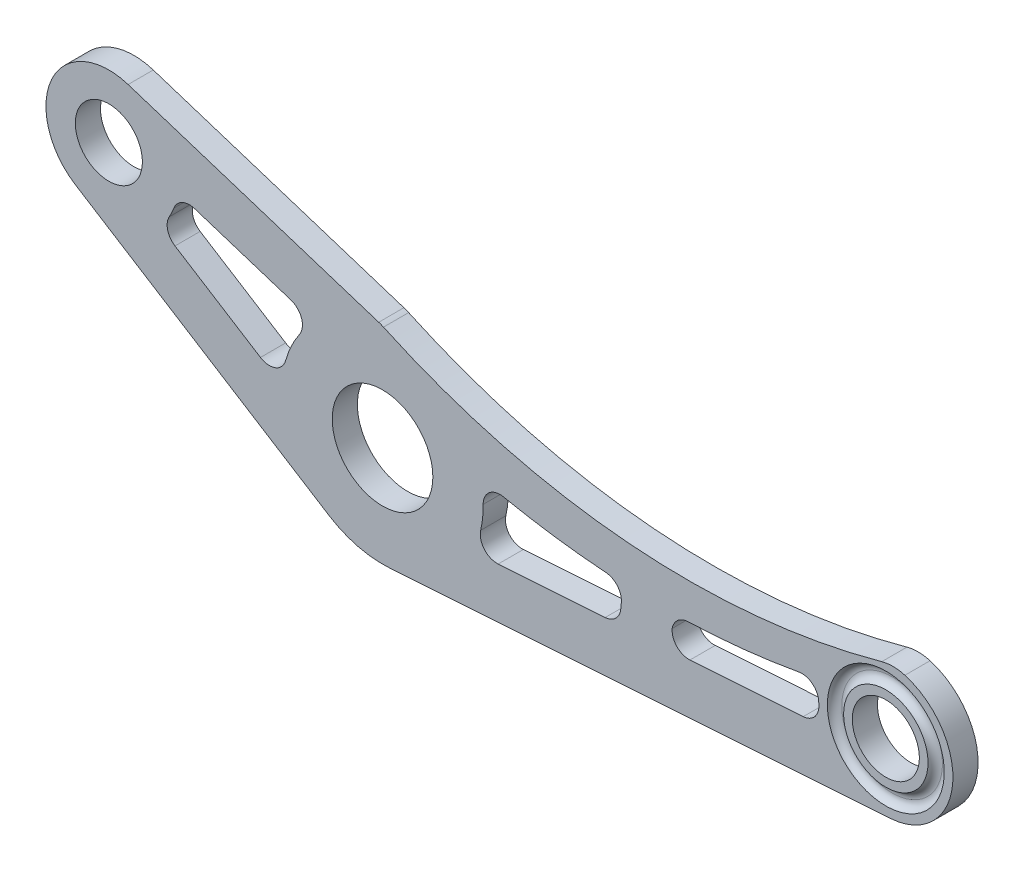
SolidWorks part; units mm, degrees
material "6061 合金"
ref_plane "前视基准面" through (0, 0, 0) normal (0, 0, 1) x (1, 0, 0)
ref_plane "上视基准面" through (0, 0, 0) normal (0, 1, 0) x (1, 0, 0)
ref_plane "右视基准面" through (0, 0, 0) normal (1, 0, 0) x (0, 0, -1)
other "Configuration Table"
sketch "草图1" plane through (0, 0, 0) normal (0, 0, 1) x (1, 0, 0)
  line L0 (0, 0) -> (60, 0)
  line L1 (0, 0) -> (-32.6271, 15.2143)
  line L2 (60.5333, -7.9822) -> (0.8, -11.9733)
  line L3 (4.7194, 11.7114) -> (60.5333, 7.9822)
  line L4 (-36.6215, 8.8665) -> (-6.3911, -10.1565)
  line L5 (-30.332, 22.3545) -> (-0.0675, 12.6264)
  arc A0 (-6.3911, -10.1565) -> (0.8, -11.9733) centre (0, 0) ccw
  arc A1 (-30.332, 22.3545) -> (-36.6215, 8.8665) centre (-32.6271, 15.2143) ccw
  arc A2 (60.5333, -7.9822) -> (60.5333, 7.9822) centre (60, 0) ccw
  arc A4 (4.7194, 11.7114) -> (-0.0675, 12.6264) centre (6.0528, 31.6669) cw
  dimension "D4" = 16
  dimension "D5" = 15
  dimension "D6" = 24
  dimension "D7" = 20
  dimension "D1" = 60
  dimension "D2" = 36
  dimension "D3" = 155
extrude "凸台-拉伸1" add sketch "草图1" along normal blind 3 contours L3 A4 L5 A1 L4 A0 L2 A2 region at (12.4558, 2.833, 0)
sketch "草图2" plane through (0, 0, 3) normal (0, 0, 1) x (1, 0, 0)
  circle A0 centre (-32.6271, 15.2143) radius 4
  circle A1 centre (60, 0) radius 4
  circle A2 centre (0, 0) radius 6
  dimension "D1" = 8
  dimension "D2" = 8
  dimension "D3" = 12
extrude "切除-拉伸1" cut sketch "草图2" against normal blind 5
sketch "草图3" plane through (0, 0, 3) normal (0, 0, 1) x (1, 0, 0)
  line L4 (32.6264, 9.8468) -> (30.6667, -9.9778)
  line L5 (4.7194, 11.7114) -> (60.5333, 7.9822) construction
  line L6 (60.5333, -7.9822) -> (0.8, -11.9733) construction
  line L7 (29.6409, 10.1419) -> (27.6812, -9.6826)
  line L8 (60.1333, 1.9956) -> (4.3194, 5.7248)
  line L9 (-1.9036, 6.9142) -> (-32.1681, 16.6423)
  line L10 (-33.426, 13.9447) -> (-3.1956, -5.0782)
  line L11 (0.4, -5.9867) -> (60.1333, -1.9956)
  line L12 (60.1333, 1.9956) -> (4.3194, 5.7248)
  line L13 (-1.9036, 6.9142) -> (-32.1681, 16.6423)
  line L14 (-33.426, 13.9447) -> (-3.1956, -5.0782)
  line L15 (0.4, -5.9867) -> (60.1333, -1.9956)
  line L16 (35.6118, 9.5517) -> (33.6521, -10.2729)
  circle A4 centre (0, 0) radius 12
  circle A5 centre (-32.6271, 15.2143) radius 8.2703
  circle A6 centre (60, 0) radius 8
  arc A8 (-1.9036, 6.9142) -> (4.3194, 5.7248) centre (6.0528, 31.6669) ccw
  arc A9 (-32.1681, 16.6423) -> (-33.426, 13.9447) centre (-32.6271, 15.2143) ccw
  arc A10 (-3.1956, -5.0782) -> (0.4, -5.9867) centre (0, 0) ccw
  arc A11 (60.1333, -1.9956) -> (60.1333, 1.9956) centre (60, 0) ccw
  arc A12 (-1.9036, 6.9142) -> (4.3194, 5.7248) centre (6.0528, 31.6669) ccw
  arc A13 (-32.1681, 16.6423) -> (-33.426, 13.9447) centre (-32.6271, 15.2143) ccw
  arc A14 (-3.1956, -5.0782) -> (0.4, -5.9867) centre (0, 0) ccw
  arc A15 (60.1333, -1.9956) -> (60.1333, 1.9956) centre (60, 0) ccw
  dimension "D1" = 6
  dimension "D2" = 3
  dimension "D3" = 3
extrude "切除-拉伸2" cut sketch "草图3" against normal blind 10 contours A4 L15 L7 L12 | A5 L14 A4 L13 | A6 L12 L16 L15 region at (42.8536, -0.0306, 3) region at (19.771, 0.0286, 3) region at (-17.2239, 8.0316, 3)
fillet "圆角1" radius 2 12 edges at (52.4046, -2.5119, 1.5) (34.2997, -3.7216, 1.5) (35.0307, 3.6728, 1.5) (52.4046, 2.5119, 1.5) (10.7692, 5.2938, 1.5) (29.041, 4.073, 1.5) (28.2304, -4.1272, 1.5) (10.7692, -5.2938, 1.5) (-24.4251, 14.1534, 1.5) (-8.0577, 8.8924, 1.5) (-11.9913, 0.4566, 1.5) (-26.5423, 9.6131, 1.5)
sketch "草图4" plane through (0, 0, 3) normal (0, 0, 1) x (1, 0, 0)
  circle A0 centre (36.4039, 91.051) radius 86.5023
  circle A1 centre (36.4039, 91.051) radius 98.0588 construction
  circle A2 centre (60, 0) radius 4 construction
sketch "草图5" plane through (0, 0, 3) normal (0, 0, 1) x (1, 0, 0)
  line L0 (-30.332, 22.3545) -> (-0.0675, 12.6264) construction
  line L1 (-24.5404, 20.4928) -> (-0.0675, 12.6264)
  arc A0 (-24.5404, 20.4928) -> (65.3351, 5.9612) centre (33.25, 92.7183) ccw
  circle A2 centre (0, 0) radius 6 construction
  circle A3 centre (60, 0) radius 4 construction
  arc A4 (-0.0675, 12.6264) -> (59.9446, 7.9998) centre (36.0489, 89.5718) ccw
  arc A6 (65.3351, 5.9612) -> (59.9446, 7.9998) centre (60, 0) ccw
  dimension "D1" = 185
  dimension "D2" = 8
  dimension "D3" = 85
extrude "凸台-拉伸2" add sketch "草图5" against normal blind 3
fillet "圆角3" radius 2 4 edges at (51.4827, 2.0331, 1.5) (34.6903, 0.2295, 1.5) (28.6712, 0.3317, 1.5) (11.6804, 2.7683, 1.5)
sketch "草图6" plane through (0, 0, 0) normal (0, 0, -1) x (-1, 0, 0)
  circle A0 centre (-60, 0) radius 8
  dimension "D1" = 16
extrude "凸台-拉伸3" add sketch "草图6" along normal blind 0.25
sketch "草图7" plane through (0, 0, -0.25) normal (0, 0, -1) x (-1, 0, 0)
  circle A0 centre (-60, 0) radius 6 construction
  circle A1 centre (-60, 0) radius 7
  circle A2 centre (-60, 0) radius 5
  dimension "D1" = 12
  dimension "D2" = 1
  dimension "D3" = 1
extrude "切除-拉伸4" cut sketch "草图7" against normal blind 1
extrude "切除-拉伸5" cut sketch "草图4" against normal blind 11
fillet "圆角5" radius 5 2 edges at (-0.1589, 12.6558, 1.5) (60.5333, 7.9822, 1.375)
fillet "圆角6" radius 1 2 edges at (55, 0, 0.75) (53, 0, 0.75)
sketch "草图8" plane through (0, 0, -0.25) normal (0, 0, -1) x (-1, 0, 0)
  circle A0 centre (-60, 0) radius 14.0704
extrude "切除-拉伸6" cut sketch "草图8" against normal blind 0.25
mirror "镜向1" about plane through (0, 0, 0) normal (0, 0, 1) of bodies 114
delete or keep bodies "实体-删除/保留 1" type delete bodies bodies 114
